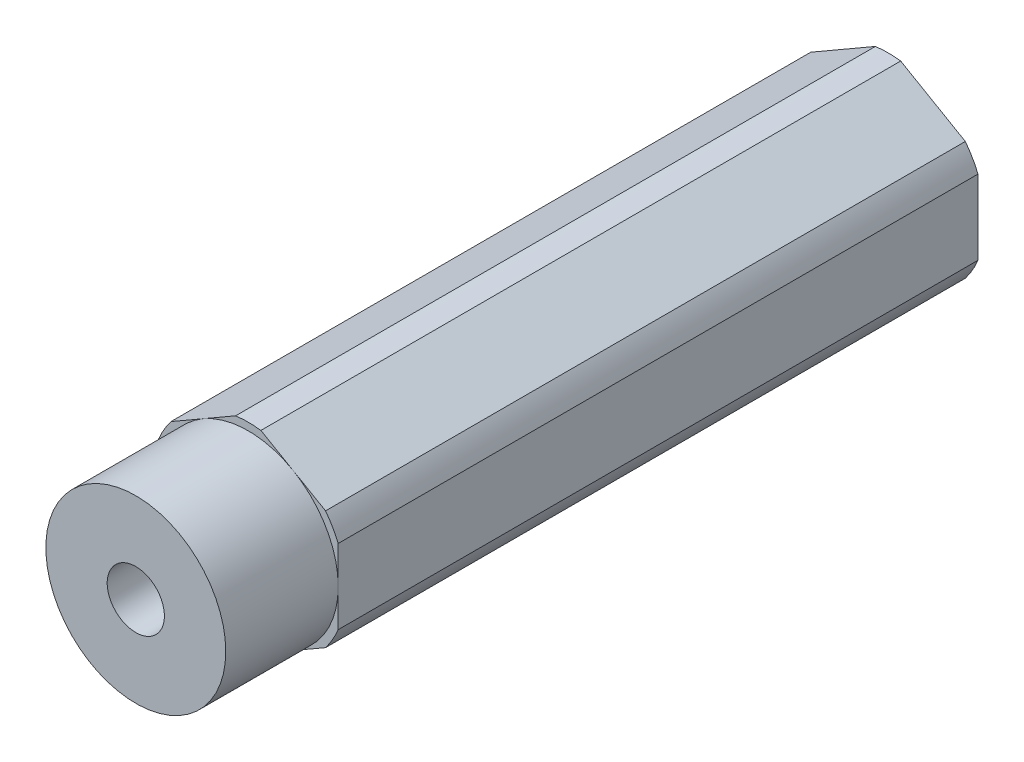
SolidWorks part; units mm, degrees
material "7075-T6 (SN)"
ref_plane "Front Plane" through (0, 0, 0) normal (0, 0, 1) x (1, 0, 0)
ref_plane "Top Plane" through (0, 0, 0) normal (0, 1, 0) x (1, 0, 0)
ref_plane "Right Plane" through (0, 0, 0) normal (1, 0, 0) x (0, 0, -1)
sketch "Sketch1" plane through (0, 0, 0) normal (0, 0, 1) x (1, 0, 0)
  line L1 (0, 7.3323) -> (-6.35, 3.6662)
  line L2 (-6.35, 3.6662) -> (-6.35, -3.6662)
  line L3 (-6.35, -3.6662) -> (0, -7.3323)
  line L4 (0, -7.3323) -> (6.35, -3.6662)
  line L5 (6.35, -3.6662) -> (6.35, 3.6662)
  line L6 (6.35, 3.6662) -> (0, 7.3323)
  circle A0 centre (0, 0) radius 6.35 construction
  circle A1 centre (0, 0) radius 6.875
  circle A2 centre (0, 0) radius 2.0193
  dimension "D1" = 12.7
  dimension "D2" = 4.0386
  dimension "D3" = 13.75
extrude "Boss-Extrude1" add sketch "Sketch1" along normal mid plane 53.1 contours L5 A1 L6 L1 L2 L3 L4 A2 region at (0, 6.6878, 0)
hole_wizard "#10-32 Tapped Hole1" positions "3DSketch2" profile "Sketch3" tap size "#10-32" standard "ANSI Inch"
sketch3d "3DSketch2"
  circle A0 centre (0, 0, -26.55) radius 2.0193 construction
  circle A1 centre (0, 0, 26.55) radius 2.0193 construction
  point P0 (0, 0, 26.55)
  point P2 (0, 0, -26.55)
  point P7 (0, 0, -24.5307)
  point P10 (0, 0, 28.5693)
sketch "Sketch3" plane through (0, 0, 26.55) normal (1, 0, 0) x (0, -1, 0)
  line L0 (0, 0) -> (0, 13.2428)
  line L1 (0, 13.2428) -> (2.0193, 12.0294)
  line L2 (2.0193, 12.0294) -> (2.0193, 0)
  line L5 (2.0193, 0) -> (0, 0)
  line L10 (0, 13.2428) -> (-2.0193, 12.0294) construction
  line L11 (0, -6.35) -> (0, 107.95) construction
  dimension "Tap Drill Dia." = 4.0386
  dimension "Tap Drill Depth" = 12.0294
  dimension "Drill Angle" = 118
cosmetic thread "Hole Thread1" parameters "D1"=9.652, "D2"=4.826
cosmetic thread "Hole Thread2" parameters "D1"=9.652, "D2"=4.826
sketch "Sketch5" plane through (0, 0, 26.55) normal (0, 0, 1) x (1, 0, 0)
  circle A0 centre (0, 0) radius 6.875
  circle A1 centre (0, 0) radius 6.35
  arc A2 (0.893, 6.8168) -> (-0.893, 6.8168) centre (0, 0) ccw construction
  dimension "D1" = 12.7
extrude "Cut-Extrude1" cut sketch "Sketch5" against normal blind 7.9375
equation "\"D3@Sketch1\"=13.75mm"
